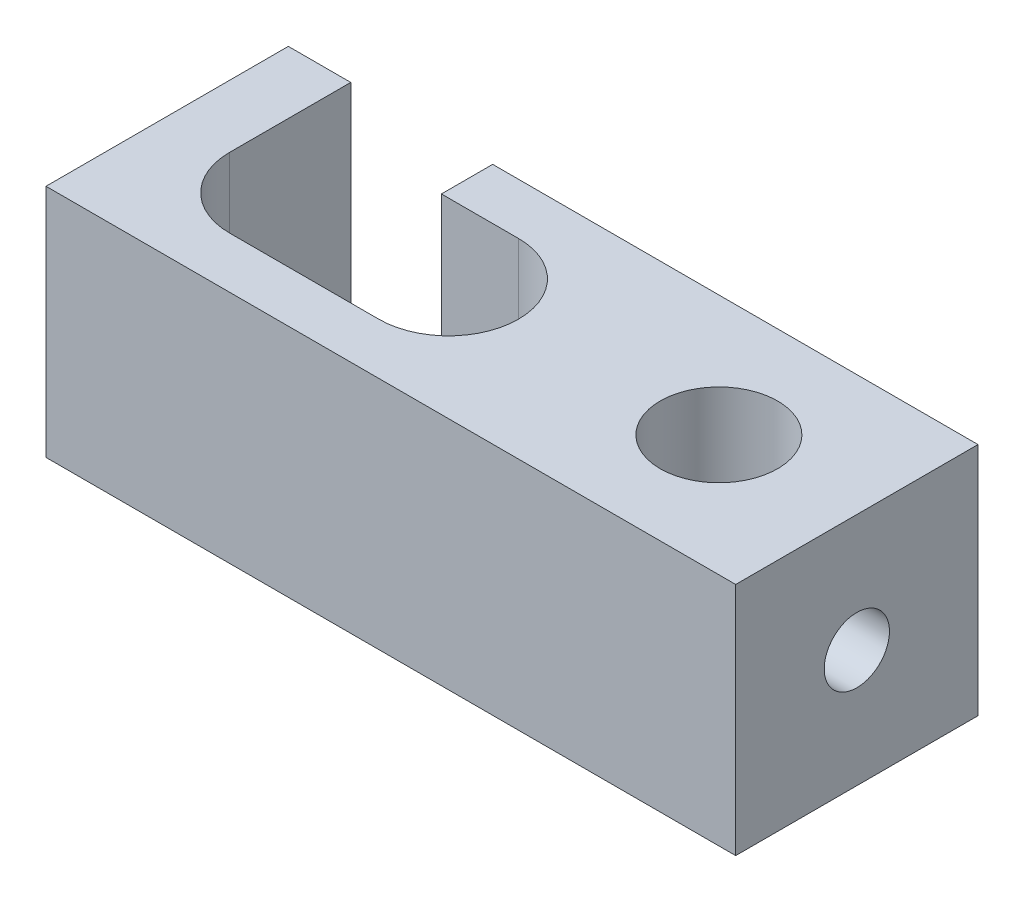
SolidWorks part; units mm, degrees
ref_plane "Front Plane" through (0, 0, 0) normal (0, 0, 1) x (1, 0, 0)
ref_plane "Top Plane" through (0, 0, 0) normal (0, 1, 0) x (1, 0, 0)
ref_plane "Right Plane" through (0, 0, 0) normal (1, 0, 0) x (0, 0, -1)
sketch "Sketch1" plane through (0, 0, 0) normal (0, 1, 0) x (1, 0, 0)
  line L0 (-13.4407, 0) -> (14.5424, 0) construction
  line L1 (-9.25, 3.25) -> (9.25, 3.25)
  line L2 (-9.25, 3.25) -> (-9.25, -3.25)
  line L3 (-9.25, -3.25) -> (9.25, -3.25)
  line L4 (9.25, 3.25) -> (9.25, -3.25)
  line L5 (-9.25, 3.25) -> (9.25, -3.25) construction
  line L6 (-9.25, -3.25) -> (9.25, 3.25) construction
  line L7 (0, 19.4234) -> (0, -7.036) construction
  line L8 (-5.7, 0) -> (-1.7, 0) construction
  line L9 (-5.7, 1.875) -> (-1.7, 1.875)
  line L10 (-5.7, -1.875) -> (-1.7, -1.875)
  line L11 (-3.7, -6.244) -> (-3.7, 9.994) construction
  line L16 (-7.575, 0) -> (-7.575, 3.25)
  line L17 (-7.575, 0) -> (-3.7683, 0)
  line L18 (-7.575, 3.25) -> (-3.7683, 3.25)
  line L19 (-3.7683, 0) -> (-3.7683, 3.25)
  circle A0 centre (5.55, 0) radius 1.575
  arc A1 (-5.7, 1.875) -> (-5.7, -1.875) centre (-5.7, 0) ccw
  arc A2 (-1.7, -1.875) -> (-1.7, 1.875) centre (-1.7, 0) ccw
  point P0 (0, 0)
  point P14 (-3.7, 0)
  point P20 (0, 6.1937)
  point P29 (-3.7, 1.875)
  dimension "D3" = 3.15
  dimension "D1" = 6.5
  dimension "D2" = 18.5
  dimension "D4" = 4
  dimension "D5" = 3.75
  dimension "D6" = 3.7
  dimension "D7" = 3.7
extrude "Boss-Extrude1" add sketch "Sketch1" along normal blind 3.15 and the other way blind 3.15 contours L4 L1 L2 L3 A2 L10 A1 L17 L19 L18 L9 A0 region at (1.0967, 0, 0.1804)
hole_wizard "M2x0.25 Tapped Hole1" positions "Sketch4" profile "Sketch5" tap size "M2x0.25" standard "DIN" end condition up to next
sketch "Sketch4" plane through (-9.25, 0, 0) normal (-1, 0, 0) x (0, 0, 1)
  point P0 (0, 0)
sketch "Sketch5" plane through (-9.25, 0, 0) normal (0, 1, 0) x (0, 0, 1)
  line L0 (0, 0) -> (0, 1.675)
  line L1 (0, 1.675) -> (0.875, 1.675)
  line L2 (0.875, 1.675) -> (0.875, 0)
  line L5 (0.875, 0) -> (0, 0)
  line L11 (0, -6.35) -> (0, 107.95) construction
  dimension "Thru Tap Drill Dia." = 1.75
  dimension "Thru Tap Drill Depth" = 1.675
cosmetic thread "Hole Thread1" parameters "D2"=2
hole_wizard "M2x0.25 Tapped Hole2" positions "Sketch6" profile "Sketch7" tap size "M2x0.25" standard "DIN" end condition up to next
sketch "Sketch6" plane through (9.25, 0, 0) normal (1, 0, 0) x (0, 0, -1)
  point P0 (0, 0)
sketch "Sketch7" plane through (9.25, 0, 0) normal (0, 1, 0) x (0, 0, -1)
  line L0 (0, 0) -> (0, 2.125)
  line L1 (0, 2.125) -> (0.875, 2.125)
  line L2 (0.875, 2.125) -> (0.875, 0)
  line L5 (0.875, 0) -> (0, 0)
  line L11 (0, -6.35) -> (0, 107.95) construction
  dimension "Thru Tap Drill Dia." = 1.75
  dimension "Thru Tap Drill Depth" = 2.125
cosmetic thread "Hole Thread2" parameters "D2"=2
equation "\"D6@Sketch1\"=\"D2@Sketch1\"/5"
equation "\"D7@Sketch1\"=\"D2@Sketch1\"/5"
